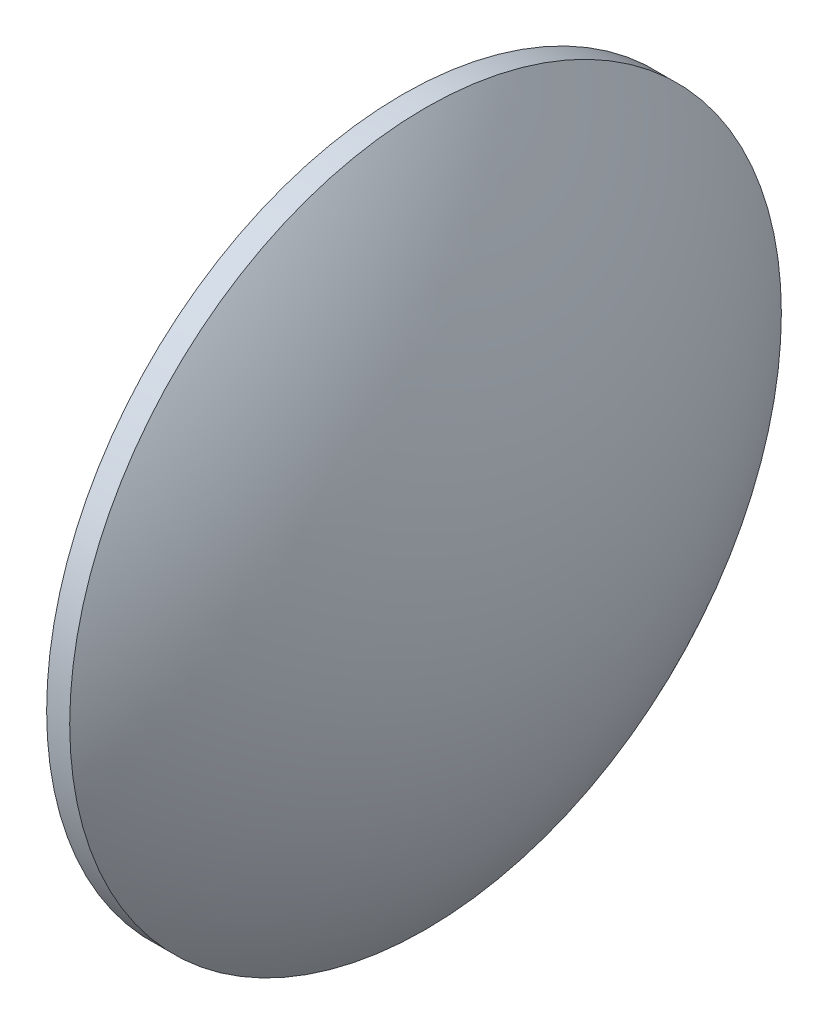
SolidWorks part; units mm, degrees
ref_plane "Front Plane" through (0, 0, 0) normal (0, 0, 1) x (1, 0, 0)
ref_plane "Top Plane" through (0, 0, 0) normal (0, 1, 0) x (1, 0, 0)
ref_plane "Right Plane" through (0, 0, 0) normal (1, 0, 0) x (0, 0, -1)
sketch "Sketch1" plane through (0, 0, 0) normal (1, 0, 0) x (0, 0, -1)
  circle A0 centre (0, 0) radius 30.8511
extrude "Boss-Extrude1" add sketch "Sketch1" along normal blind 2
dome "Dome1" faces to dome 1 distance 10 reverse direction no elliptical dome no face at (2, 0, -30.8511) parameters "D1"=10
dome "Dome2" faces to dome 1 distance 10 reverse direction no elliptical dome no face at (0, 0, -30.8511) parameters "D1"=10
